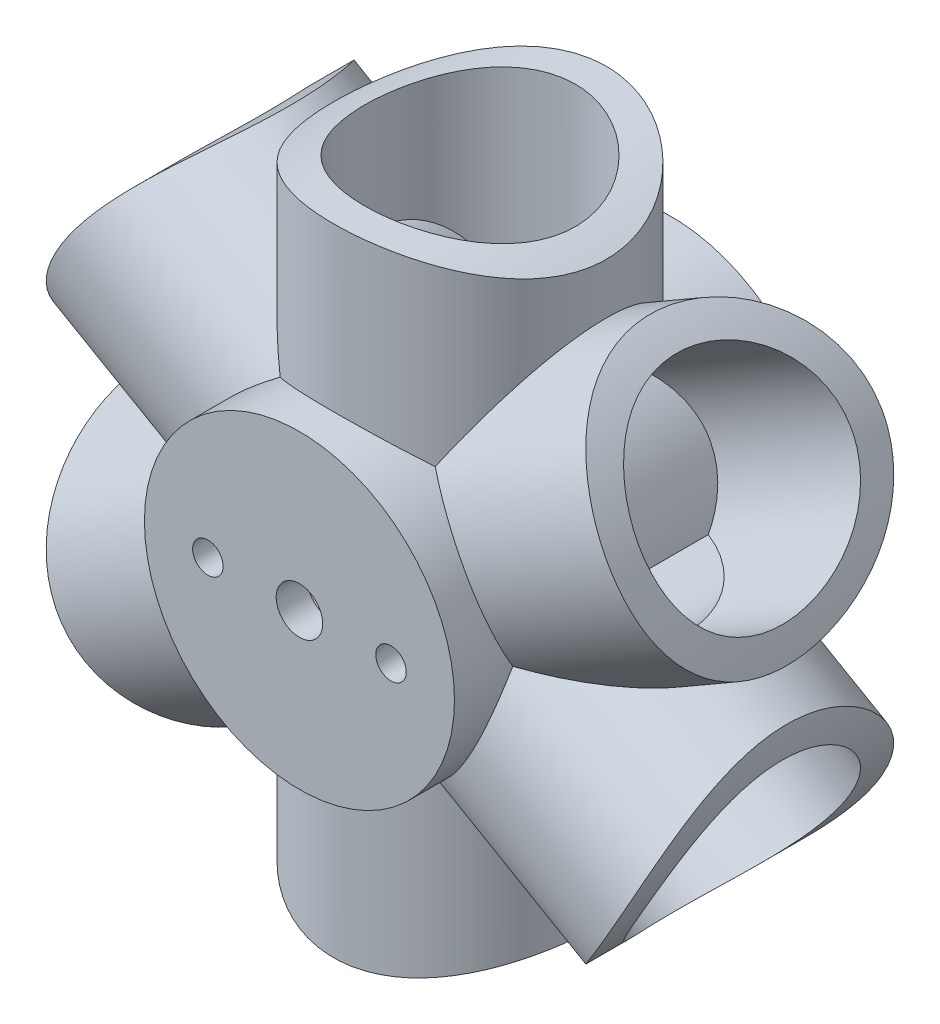
SolidWorks part; units mm, degrees
ref_plane "Front Plane" through (0, 0, 0) normal (0, 0, 1) x (1, 0, 0)
ref_plane "Top Plane" through (0, 0, 0) normal (0, 1, 0) x (1, 0, 0)
ref_plane "Right Plane" through (0, 0, 0) normal (1, 0, 0) x (0, 0, -1)
sketch "Sketch1" plane through (0, 0, 0) normal (0, 1, 0) x (1, 0, 0)
  circle A0 centre (0, 0) radius 11.176
  circle A1 centre (0, 0) radius 8.636
  dimension "D1" = 22.352
  dimension "D2" = 17.272
extrude "Boss-Extrude1" add sketch "Sketch1" along normal blind 20.32
sketch "Sketch2" plane through (0, 0, 0) normal (0, 0, 1) x (1, 0, 0)
  line L0 (11.176, 20.32) -> (-11.176, 20.32) construction
  line L1 (-8.636, 20.32) -> (-11.176, 20.32)
  line L2 (8.4632, 20.32) -> (11.0032, 20.32)
  line L3 (0, 20.32) -> (0, 38.4954) construction
  arc A2 (8.4632, 20.32) -> (-8.636, 20.32) centre (-0.0864, 7.6039) ccw
  arc A3 (11.0032, 20.32) -> (-11.176, 20.32) centre (-0.0864, 7.6039) ccw
revolve "Revolve1" add sketch "Sketch2" angle 360 about L3 region at (-9.906, 20.5457, 0)
ref_plane "Plane1" through (0, 27.94, 0) normal (0, -1, 0) x (-1, 0, 0)
sketch "Sketch3" plane through (0, 27.94, 0) normal (0, -1, 0) x (-1, 0, 0)
  line L0 (0, 11.9871) -> (0, -12.3331)
pattern_circular "CirPattern1" count 6 over 360 about axis through (0, 27.94, -11.9871) along (0, 0, 1) of bodies 103
sketch "Sketch4" plane through (0, 0, 0) normal (0, 0, 1) x (1, 0, 0)
  circle A0 centre (0, 27.94) radius 12.7
  dimension "D1" = 25.4
extrude "Boss-Extrude2" add sketch "Sketch4" along normal blind 13.97 and the other way blind 16.51
sketch "Sketch5" plane through (0, 0, 13.97) normal (0, 0, 1) x (1, 0, 0)
  circle A0 centre (0, 27.94) radius 26.035
  circle A1 centre (0, 27.94) radius 34.3456
  dimension "D1" = 52.07
extrude "Cut-Extrude1" cut sketch "Sketch5" against normal through all
sketch "Sketch8" plane through (0, 0, 0) normal (0, 1, 0) x (1, 0, 0)
  circle A0 centre (0, 0) radius 8.636
extrude "Cut-Extrude2" cut sketch "Sketch8" along normal up to surface (15.24 mm away) up to face at (0.2598, 15.3358, 2.1433)
pattern_circular "CirPattern2" count 6 over 360 about axis through (0, 27.94, -16.51) along (0, 0, 1) of "Cut-Extrude2"
sketch "Sketch9" plane through (0, 0, -16.51) normal (0, 0, -1) x (-1, 0, 0)
  line L0 (-159.3608, -65.013) -> (-26.0275, -65.013) construction
  line L1 (-5.3001, 25.0893) -> (-5.3001, 24.6378)
  line L2 (-5.3001, 32.5511) -> (5.1143, 32.5511)
  line L3 (-6.5701, 31.2811) -> (-6.5701, 23.7722)
  line L4 (-5.3001, 22.5022) -> (5.1143, 22.5022)
  line L5 (6.3843, 31.2811) -> (6.3843, 23.7722)
  line L6 (-4.9342, 31.6555) -> (4.7922, 31.6555)
  line L7 (-5.6962, 30.8935) -> (-5.6962, 24.1162)
  line L8 (-4.9342, 23.3542) -> (4.7922, 23.3542)
  line L9 (5.5542, 30.8935) -> (5.5542, 24.1162)
  line L10 (-5.3001, 24.6378) -> (-3.6843, 24.6378)
  line L11 (-3.6843, 24.6378) -> (-3.6843, 25.0893)
  line L12 (-3.6843, 25.0893) -> (-4.0153, 25.0893)
  line L13 (-4.0153, 25.0893) -> (-2.7662, 29.1074)
  line L14 (-2.7662, 29.1074) -> (-0.7496, 27.3015)
  line L15 (-0.7496, 27.3015) -> (-0.7496, 24.8635)
  line L16 (-0.7496, 24.8635) -> (-1.5021, 24.8635)
  line L17 (-1.5021, 24.8635) -> (-1.5021, 24.4572)
  line L18 (-1.5021, 24.4572) -> (-0.2379, 24.4572)
  line L19 (-0.2379, 24.4572) -> (-0.2379, 31.2811)
  line L20 (-0.2379, 31.2811) -> (-1.7579, 31.2811)
  line L21 (-1.7579, 31.2811) -> (-1.7579, 30.7478)
  line L22 (-1.7579, 30.7478) -> (-0.7496, 30.7478)
  line L23 (-0.7496, 30.7478) -> (-0.7496, 28.656)
  line L24 (-0.7496, 28.656) -> (-2.6007, 30.507)
  line L25 (-2.6007, 30.507) -> (-4.3163, 25.0893)
  line L26 (-4.3163, 25.0893) -> (-5.3001, 25.0893)
  line L27 (-0.071, 31.6555) -> (-0.071, 23.3542) construction
  line L28 (2.4587, 30.507) -> (4.1743, 25.0893)
  line L29 (0.6076, 28.656) -> (2.4587, 30.507)
  line L30 (0.6076, 30.7478) -> (0.6076, 28.656)
  line L31 (1.6159, 30.7478) -> (0.6076, 30.7478)
  line L32 (1.6159, 31.2811) -> (1.6159, 30.7478)
  line L33 (0.0959, 31.2811) -> (1.6159, 31.2811)
  line L34 (0.0959, 24.4572) -> (0.0959, 31.2811)
  line L35 (1.3601, 24.4572) -> (0.0959, 24.4572)
  line L36 (1.3601, 24.8635) -> (1.3601, 24.4572)
  line L37 (0.6076, 24.8635) -> (1.3601, 24.8635)
  line L38 (0.6076, 27.3015) -> (0.6076, 24.8635)
  line L39 (2.6242, 29.1074) -> (0.6076, 27.3015)
  line L40 (3.8733, 25.0893) -> (2.6242, 29.1074)
  line L41 (3.5422, 25.0893) -> (3.8733, 25.0893)
  line L42 (3.5422, 24.6378) -> (3.5422, 25.0893)
  line L43 (5.158, 24.6378) -> (3.5422, 24.6378)
  line L44 (5.158, 25.0893) -> (5.158, 24.6378)
  line L45 (4.1743, 25.0893) -> (5.158, 25.0893)
  line L47 (-5.3001, 24.3067) -> (5.1143, 24.3067)
  line L48 (-5.3001, 24.3067) -> (-5.3001, 23.8703)
  line L49 (-5.3001, 23.8703) -> (5.1143, 23.8703)
  line L50 (5.1143, 24.3067) -> (5.1143, 23.8703)
  arc A0 (5.1143, 32.5511) -> (6.3843, 31.2811) centre (5.1143, 31.2811) cw
  arc A1 (5.1143, 22.5022) -> (6.3843, 23.7722) centre (5.1143, 23.7722) ccw
  arc A2 (-6.5701, 23.7722) -> (-5.3001, 22.5022) centre (-5.3001, 23.7722) ccw
  arc A3 (-5.3001, 32.5511) -> (-6.5701, 31.2811) centre (-5.3001, 31.2811) ccw
  arc A4 (4.7922, 31.6555) -> (5.5542, 30.8935) centre (4.7922, 30.8935) cw
  arc A5 (4.7922, 23.3542) -> (5.5542, 24.1162) centre (4.7922, 24.1162) ccw
  arc A6 (-5.6962, 24.1162) -> (-4.9342, 23.3542) centre (-4.9342, 24.1162) ccw
  arc A7 (-4.9342, 31.6555) -> (-5.6962, 30.8935) centre (-4.9342, 30.8935) ccw
  dimension "D1" = 1.27
  dimension "D2" = 0.762
extrude "Cut-Extrude3" [suppressed] cut sketch "Sketch9" against normal blind 1.27 contours L25 L26 L1 L10 L11 L12 L13 L14 L15 L16 L17 L18 L19 L20 L21 L22 L23 L24 | L45 L28 L29 L30 L31 L32 L33 L34 L35 L36 L37 L38 L39 L40 L41 L42 L43 L44 | L2 A3 L3 A2 L4 A1 L5 A0 A7 L6 A4 L9 A5 L8 A6 L7
sketch "Sketch10" plane through (0, 0, 13.97) normal (0, 0, 1) x (1, 0, 0)
  circle A0 centre (0, 27.94) radius 1.905
  arc A1 (-6.35, 38.9385) -> (-12.7, 27.94) centre (0, 27.94) ccw construction
  dimension "D1" = 3.81
extrude "Cut-Extrude4" cut sketch "Sketch10" against normal blind 2.54 contours A0
sketch "Sketch12" plane through (0, 0, 0) normal (0, 0, 1) x (1, 0, 0)
  line L1 (-12.7, 27.94) -> (-17.272, 27.94) construction
  arc A2 (-6.35, 38.9385) -> (-12.7, 27.94) centre (0, 27.94) ccw construction
  ellipse E0 centre (-12.7, 27.94) end of major axis (-17.78, 27.94) minor radius 1.27
  dimension "D1" = 10.16
  dimension "D2" = 2.54
extrude "Boss-Extrude3" add sketch "Sketch12" along normal up to next and the other way up to next
pattern_circular "CirPattern3" count 6 over 360 about axis through (0, 27.94, -16.51) along (0, 0, 1) of "Boss-Extrude3"
sketch "Sketch13" plane through (0, 0, -16.51) normal (0, 0, -1) x (-1, 0, 0)
  circle A0 centre (0, 27.94) radius 3.175
  circle A1 centre (0, 27.94) radius 12.7 construction
  dimension "D1" = 6.35
extrude "Cut-Extrude5" cut sketch "Sketch13" against normal up to surface (27.94 mm away) up to face at (1.905, 27.94, 11.43)
sketch "Sketch14" plane through (0, 0, 13.97) normal (0, 0, 1) x (1, 0, 0)
  circle A0 centre (-7.5, 27.94) radius 1.25
  circle A1 centre (7.5, 27.94) radius 1.25
  point P4 (0, 0)
  point P5 (0, 27.94)
  dimension "D1" = 2.5
  dimension "D2" = 7.5
  dimension "D3" = 7.5
extrude "Cut-Extrude6" cut sketch "Sketch14" against normal blind 7
